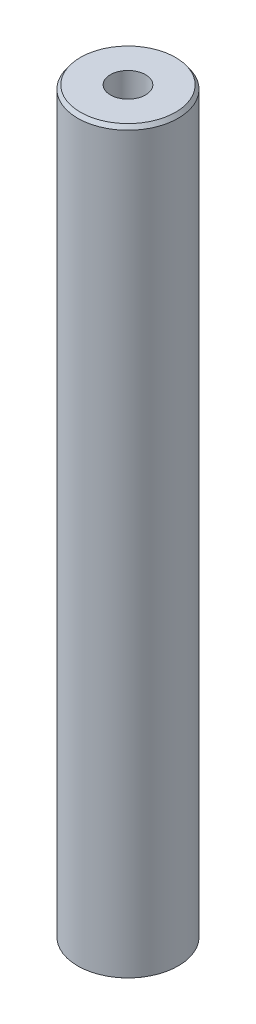
SolidWorks part; units mm, degrees
ref_plane "Front Plane" through (0, 0, 0) normal (0, 0, 1) x (1, 0, 0)
ref_plane "Top Plane" through (0, 0, 0) normal (0, 1, 0) x (1, 0, 0)
ref_plane "Right Plane" through (0, 0, 0) normal (1, 0, 0) x (0, 0, -1)
sketch "Sketch1" plane through (0, 0, 0) normal (0, 1, 0) x (1, 0, 0)
  circle A0 centre (0, 0) radius 40
  dimension "SHAFT_OD" = 80
extrude "Boss-Extrude1" add sketch "Sketch1" along normal blind 589.2489
sketch "Sketch2" plane through (0, 0, 0) normal (0, 1, 0) x (1, 0, 0)
  circle A0 centre (0, 0) radius 13.9982
  dimension "BORE_D" = 27.9963
extrude "Cut-Extrude1" cut sketch "Sketch2" along normal through all
chamfer "Chamfer1" distance 3.039 angle 35.67 2 edges at (0, 589.2489, 40) (0, 0, 40) first distance on face at (0, 589.2489, 40) first distance on face at (0, 0, 13.9982)
